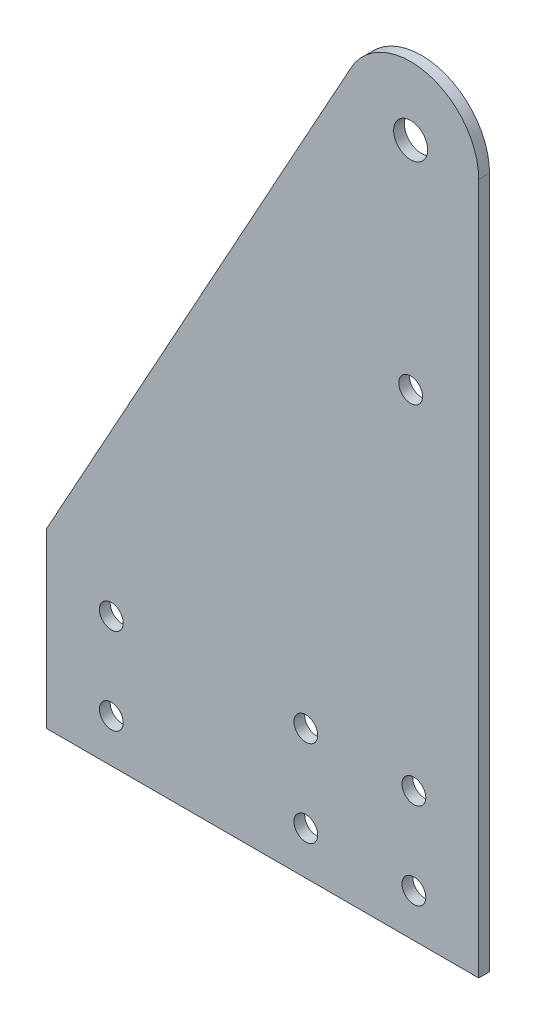
SolidWorks part; units mm, degrees
ref_plane "Front Plane" through (0, 0, 0) normal (0, 0, 1) x (1, 0, 0)
ref_plane "Top Plane" through (0, 0, 0) normal (0, 1, 0) x (1, 0, 0)
ref_plane "Right Plane" through (0, 0, 0) normal (1, 0, 0) x (0, 0, -1)
sketch "Sketch1" plane through (0, 0, 0) normal (0, 0, 1) x (1, 0, 0)
  line L0 (-63.5, -25.4) -> (63.5, -25.4)
  line L2 (63.5, -25.4) -> (63.5, 177.8)
  line L3 (25.9919, 187.4678) -> (-63.5, 25.4)
  line L5 (-63.5, 25.4) -> (-63.5, -25.4)
  line L6 (-63.5, 25.4) -> (63.5, -25.4) construction
  line L7 (44.45, 12.7) -> (12.7, 12.7) construction
  line L8 (-44.45, -12.7) -> (44.45, -12.7) construction
  line L9 (-44.45, -12.7) -> (-44.45, 12.7) construction
  line L10 (-44.45, 12.7) -> (44.45, 12.7) construction
  line L11 (44.45, -12.7) -> (44.45, 12.7) construction
  line L12 (-44.45, -12.7) -> (44.45, 12.7) construction
  line L13 (-44.45, 12.7) -> (44.45, -12.7) construction
  arc A0 (25.9919, 187.4678) -> (63.5, 177.8) centre (43.5, 177.8) cw
  circle A1 centre (43.5, 177.8) radius 5
  circle A2 centre (-44.45, 12.7) radius 3.5
  circle A3 centre (44.45, 12.7) radius 3.5
  circle A4 centre (44.45, -12.7) radius 3.5
  circle A5 centre (-44.45, -12.7) radius 3.5
  circle A6 centre (12.7, 12.7) radius 3.5
  circle A7 centre (12.7, -12.7) radius 3.5
  circle A8 centre (43.5, 114.3) radius 3.5
  point P7 (0, 0)
  point P8 (0, 0)
  point P24 (0, 0)
  dimension "D2" = 10
  dimension "D6" = 20
  dimension "D5" = 7
  dimension "D10" = 63.5
  dimension "D1" = 50.8
  dimension "D3" = 127
  dimension "D4" = 152.4
  dimension "D7" = 25.4
  dimension "D8" = 88.9
  dimension "D9" = 31.75
extrude "Boss-Extrude1" add sketch "Sketch1" along normal blind 3.175
